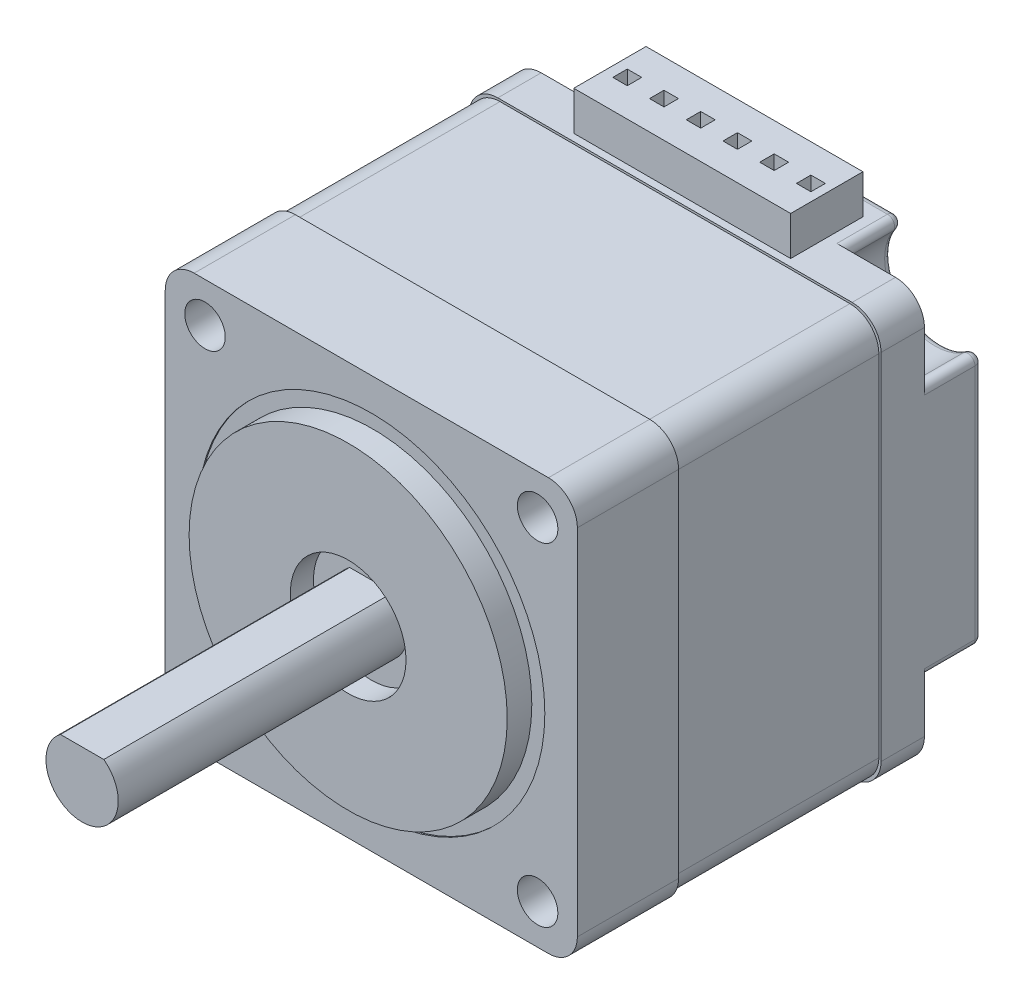
SolidWorks part; units mm, degrees
material "1060 Alloy"
ref_plane "Front Plane" through (0, 0, 0) normal (0, 0, 1) x (1, 0, 0)
ref_plane "Top Plane" through (0, 0, 0) normal (0, 1, 0) x (1, 0, 0)
ref_plane "Right Plane" through (0, 0, 0) normal (1, 0, 0) x (0, 0, -1)
sketch "Sketch1" plane through (0, 0, 0) normal (0, 0, 1) x (1, 0, 0)
  line L1 (-14.25, 14.25) -> (14.25, 14.25)
  line L2 (-14.25, 14.25) -> (-14.25, -14.25)
  line L3 (-14.25, -14.25) -> (14.25, -14.25)
  line L4 (14.25, 14.25) -> (14.25, -14.25)
  line L5 (-14.25, 14.25) -> (14.25, -14.25) construction
  line L6 (-14.25, -14.25) -> (14.25, 14.25) construction
  point P0 (0, 0)
  dimension "D1" = 28.5
extrude "Boss-Extrude1" add sketch "Sketch1" along normal blind 7
fillet "Fillet1" radius 2 4 edges at (14.25, -14.25, 3.5) (-14.25, -14.25, 3.5) (14.25, 14.25, 3.5) (-14.25, 14.25, 3.5)
sketch "Sketch2" plane through (0, 0, 7) normal (0, 0, 1) x (1, 0, 0)
  circle A0 centre (0, 0) radius 11
  dimension "D1" = 22
extrude "Boss-Extrude2" add sketch "Sketch2" along normal blind 1.6
sketch "Sketch3" plane through (0, 0, 8.6) normal (0, 0, 1) x (1, 0, 0)
  circle A0 centre (0, 0) radius 4
  dimension "D1" = 8
extrude "Cut-Extrude1" cut sketch "Sketch3" against normal blind 1.6
sketch "Sketch4" plane through (0, 0, 7) normal (0, 0, 1) x (1, 0, 0)
  circle A0 centre (0, 0) radius 2.5
  dimension "D1" = 5
extrude "Boss-Extrude3" add sketch "Sketch4" along normal blind 20
sketch "Sketch5" plane through (0, 0, 27) normal (0, 0, 1) x (1, 0, 0)
  line L1 (-2.2, 2) -> (2.2, 2)
  line L2 (-2.2, 2) -> (-2.2, 3)
  line L3 (-2.2, 3) -> (2.2, 3)
  line L4 (2.2, 2) -> (2.2, 3)
  circle A0 centre (0, 0) radius 2.5 construction
  dimension "D1" = 2
  dimension "D2" = 1
  dimension "D3" = 2.2
  dimension "D4" = 4.4
extrude "Cut-Extrude2" cut sketch "Sketch5" against normal blind 20
sketch "Sketch6" plane through (0, 0, 0) normal (0, 0, -1) x (-1, 0, 0)
  line L1 (-14.1, 14.1) -> (14.1, 14.1)
  line L2 (-14.1, 14.1) -> (-14.1, -14.1)
  line L3 (-14.1, -14.1) -> (14.1, -14.1)
  line L4 (14.1, 14.1) -> (14.1, -14.1)
  line L5 (-14.1, 14.1) -> (14.1, -14.1) construction
  line L6 (-14.1, -14.1) -> (14.1, 14.1) construction
  point P0 (0, 0)
  dimension "D1" = 28.2
extrude "Boss-Extrude4" add sketch "Sketch6" along normal blind 14
fillet "Fillet2" radius 2 4 edges at (-14.1, -14.1, -7) (14.1, -14.1, -7) (-14.1, 14.1, -7) (14.1, 14.1, -7)
sketch "Sketch7" plane through (0, 0, -14) normal (0, 0, -1) x (-1, 0, 0)
  line L1 (-14.25, 14.25) -> (14.25, 14.25)
  line L2 (-14.25, 14.25) -> (-14.25, -14.25)
  line L3 (-14.25, -14.25) -> (14.25, -14.25)
  line L4 (14.25, 14.25) -> (14.25, -14.25)
  line L5 (-14.25, 14.25) -> (14.25, -14.25) construction
  line L6 (-14.25, -14.25) -> (14.25, 14.25) construction
  point P0 (0, 0)
  dimension "D1" = 28.5
extrude "Boss-Extrude5" add sketch "Sketch7" along normal blind 7
fillet "Fillet3" radius 2 4 edges at (-14.25, -14.25, -17.5) (14.25, -14.25, -17.5) (-14.25, 14.25, -17.5) (14.25, 14.25, -17.5)
sketch "Sketch8" plane through (0, 14.25, 0) normal (0, 1, 0) x (1, 0, 0)
  line L0 (-12.25, 14) -> (12.25, 14) construction
  line L1 (-7.5, 19.5) -> (7.5, 19.5)
  line L2 (-7.5, 19.5) -> (-7.5, 14.5)
  line L3 (-7.5, 14.5) -> (7.5, 14.5)
  line L4 (7.5, 19.5) -> (7.5, 14.5)
  line L5 (-7.5, 19.5) -> (7.5, 14.5) construction
  line L6 (-7.5, 14.5) -> (7.5, 19.5) construction
  point P0 (0, 17)
  dimension "D1" = 5
  dimension "D2" = 15
  dimension "D3" = 0
  dimension "D4" = 0.5
extrude "Boss-Extrude6" add sketch "Sketch8" along normal blind 2.7
sketch "Sketch9" plane through (0, 0, 7) normal (0, 0, 1) x (1, 0, 0)
  circle A0 centre (-11.5, 11.5) radius 1.4
  circle A1 centre (11.5, 11.5) radius 1.4
  circle A2 centre (11.5, -11.5) radius 1.4
  circle A3 centre (-11.5, -11.5) radius 1.4
  dimension "D1" = 2.8
  dimension "D2" = 23
  dimension "D3" = 23
  dimension "D4" = 23
  dimension "D5" = 23
  dimension "D6" = 11.5
  dimension "D7" = 11.5
  dimension "D8" = 11.5
  dimension "D9" = 11.5
extrude "Cut-Extrude3" cut sketch "Sketch9" against normal blind 42.7
sketch "Sketch10" plane through (0, 0, -21) normal (0, 0, -1) x (-1, 0, 0)
  circle A0 centre (-11.5, 11.5) radius 3.5
  circle A1 centre (11.5, 11.5) radius 3.5
  circle A2 centre (11.5, -11.5) radius 3.5
  circle A3 centre (-11.5, -11.5) radius 3.5
  dimension "D1" = 7
extrude "Cut-Extrude4" cut sketch "Sketch10" against normal blind 4
fillet "Fillet4" radius 0.5 8 edges at (-14.25, 9.3349, -19) (-9.3349, 14.25, -19) (-14.25, -9.3349, -19) (-9.3349, -14.25, -19) (9.3349, -14.25, -19) (14.25, -9.3349, -19) (9.3349, 14.25, -19) (14.25, 9.3349, -19)
fillet "Fillet5" radius 0.5 16 edges at (-13.9839, -8.6348, -21) (-9.0251, -9.0251, -21) (-8.6348, -13.9839, -21) (0, -14.25, -21) (8.6348, -13.9839, -21) (9.0251, -9.0251, -21) (13.9839, -8.6348, -21) (14.25, 0, -21) (13.9839, 8.6348, -21) (9.0251, 9.0251, -21) (8.6348, 13.9839, -21) (0, 14.25, -21) (-8.6348, 13.9839, -21) (-9.0251, 9.0251, -21) (-13.9839, 8.6348, -21) (-14.25, 0, -21)
sketch "Sketch11" plane through (0, 0, 7) normal (0, 0, 1) x (1, 0, 0)
  circle A0 centre (0, 0) radius 11
  circle A1 centre (0, 0) radius 12
  dimension "D1" = 1
extrude "Cut-Extrude5" cut sketch "Sketch11" against normal blind 0.1
sketch "Sketch12" plane through (0, 0, -21) normal (0, 0, -1) x (-1, 0, 0)
  circle A0 centre (0, 0) radius 4
  dimension "D1" = 8
extrude "Cut-Extrude6" cut sketch "Sketch12" against normal blind 2.5
sketch "Sketch13" plane through (0, 0, -18.5) normal (0, 0, -1) x (-1, 0, 0)
  circle A0 centre (0, 0) radius 2.5
  dimension "D1" = 5
extrude "Boss-Extrude7" add sketch "Sketch13" along normal blind 0.5
fillet "Fillet6" radius 0.2 1 edges at (-2.5, 0, -19)
sketch "Sketch14" plane through (0, 16.95, 0) normal (0, 1, 0) x (1, 0, 0)
  line L0 (-7.5, 14.5) -> (7.5, 14.5) construction
  line L1 (-6.8, 17.5) -> (-5.8, 17.5)
  line L2 (-6.8, 17.5) -> (-6.8, 16.5)
  line L3 (-6.8, 16.5) -> (-5.8, 16.5)
  line L4 (-5.8, 17.5) -> (-5.8, 16.5)
  line L5 (-7.5, 19.5) -> (-7.5, 14.5) construction
  line L6 (-3.26, 17.5) -> (-3.26, 16.5)
  line L7 (-4.26, 17.5) -> (-3.26, 17.5)
  line L8 (-4.26, 17.5) -> (-4.26, 16.5)
  line L9 (-4.26, 16.5) -> (-3.26, 16.5)
  line L10 (-0.72, 17.5) -> (-0.72, 16.5)
  line L11 (-1.72, 17.5) -> (-0.72, 17.5)
  line L12 (-1.72, 17.5) -> (-1.72, 16.5)
  line L13 (-1.72, 16.5) -> (-0.72, 16.5)
  line L14 (1.82, 17.5) -> (1.82, 16.5)
  line L15 (0.82, 17.5) -> (1.82, 17.5)
  line L16 (0.82, 17.5) -> (0.82, 16.5)
  line L17 (0.82, 16.5) -> (1.82, 16.5)
  line L18 (4.36, 17.5) -> (4.36, 16.5)
  line L19 (3.36, 17.5) -> (4.36, 17.5)
  line L20 (3.36, 17.5) -> (3.36, 16.5)
  line L21 (3.36, 16.5) -> (4.36, 16.5)
  line L22 (6.9, 17.5) -> (6.9, 16.5)
  line L23 (5.9, 17.5) -> (6.9, 17.5)
  line L24 (5.9, 17.5) -> (5.9, 16.5)
  line L25 (5.9, 16.5) -> (6.9, 16.5)
  dimension "D1" = 1
  dimension "D2" = 1
  dimension "D3" = 2
  dimension "D4" = 0.7
  dimension "D5" = 6
extrude "Cut-Extrude7" cut sketch "Sketch14" against normal blind 5
